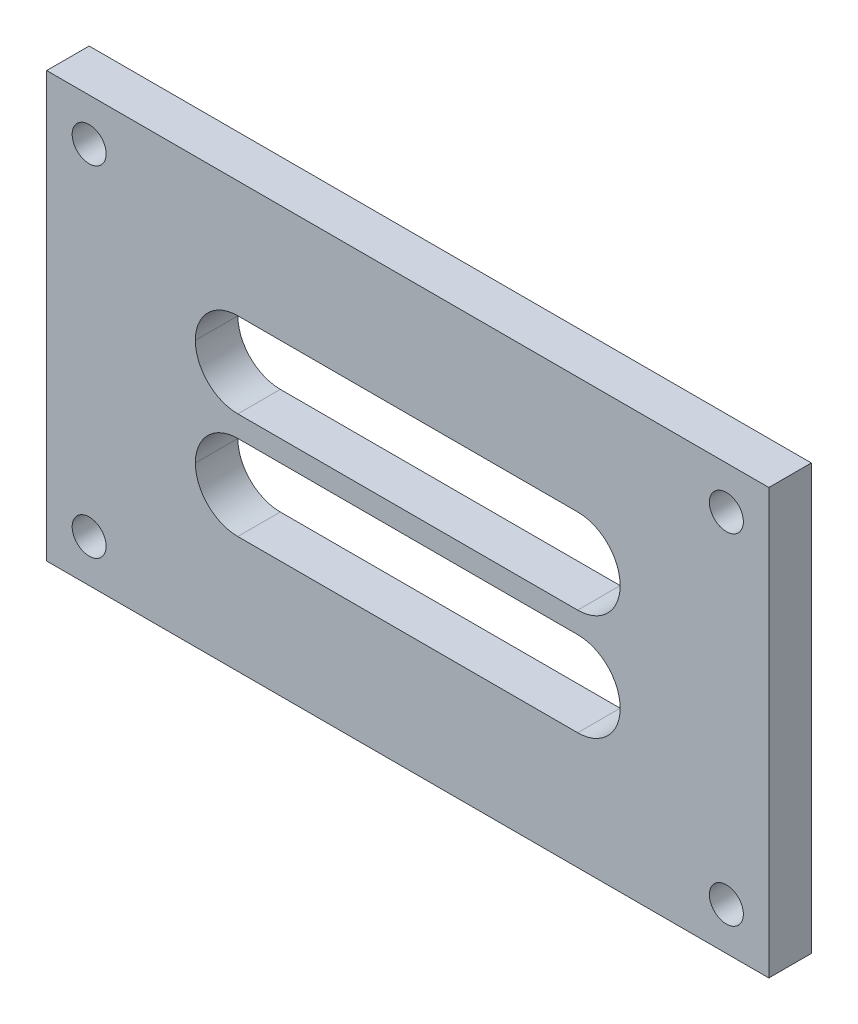
SolidWorks part; units mm, degrees
ref_plane "Front Plane" through (0, 0, 0) normal (0, 0, 1) x (1, 0, 0)
ref_plane "Top Plane" through (0, 0, 0) normal (0, 1, 0) x (1, 0, 0)
ref_plane "Right Plane" through (0, 0, 0) normal (1, 0, 0) x (0, 0, -1)
sketch "Sketch1" plane through (0, 0, 0) normal (0, 0, 1) x (1, 0, 0)
  line L0 (0, 10) -> (34, 10)
  line L1 (0, 0) -> (34, 0)
  line L2 (0, 0) -> (0, 20)
  line L3 (0, 20) -> (34, 20)
  line L4 (34, 0) -> (34, 20)
  line L5 (7, 9.5) -> (27, 9.5)
  line L6 (7, 14.5) -> (27, 14.5)
  line L7 (7, 14.5) -> (7, 10.5)
  line L8 (7, 10.5) -> (27, 10.5)
  line L9 (27, 14.5) -> (27, 10.5)
  line L10 (27, 5.5) -> (27, 9.5)
  line L11 (7, 5.5) -> (27, 5.5)
  line L12 (7, 5.5) -> (7, 9.5)
  line L13 (17, 20) -> (17, 0)
  dimension "D1" = 34
  dimension "D2" = 20
  dimension "D4" = 20
  dimension "D5" = 4
  dimension "D6" = 10
extrude "Boss-Extrude2" add sketch "Sketch1" along normal blind 2 contours L3 L13 L6 L9 L8 L0 L4 | L0 L13 L5 L10 L11 L1 L4 | L13 L0 L2 L1 L11 L12 L5 | L13 L3 L2 L0 L8 L7 L6 region at (7.4231, 15.7692, 0) region at (7.4231, 4.2308, 0) region at (26.5769, 15.7692, 0) region at (26.5769, 4.2308, 0)
ref_plane "Plane1" through (0, 0, 2) normal (0, 0, 1) x (1, 0, 0)
sketch "Sketch2" plane through (0, 0, 2) normal (0, 0, 1) x (1, 0, 0)
  line L2 (17, 20) -> (17, 0)
  line L3 (0, 20) -> (34, 20) construction
  line L4 (0, 0) -> (34, 0) construction
  line L5 (0, 10) -> (34, 10)
  line L6 (0, 0) -> (0, 20) construction
  line L7 (34, 0) -> (34, 20) construction
  circle A0 centre (2, 18) radius 0.8
  circle A1 centre (32, 18) radius 0.8
  circle A2 centre (2, 2) radius 0.8
  circle A3 centre (32, 2) radius 0.8
  dimension "D1" = 2
extrude "Cut-Extrude1" cut sketch "Sketch2" against normal blind 2 contours A2 | A0 | A1 | A3 region at (2, 18, 2) region at (32, 18, 2) region at (2, 2, 2) region at (32, 2, 2)
fillet "Fillet1" radius 2 8 edges at (7, 9.5, 1) (7, 5.5, 1) (27, 9.5, 1) (27, 5.5, 1) (27, 10.5, 1) (27, 14.5, 1) (7, 10.5, 1) (7, 14.5, 1)
